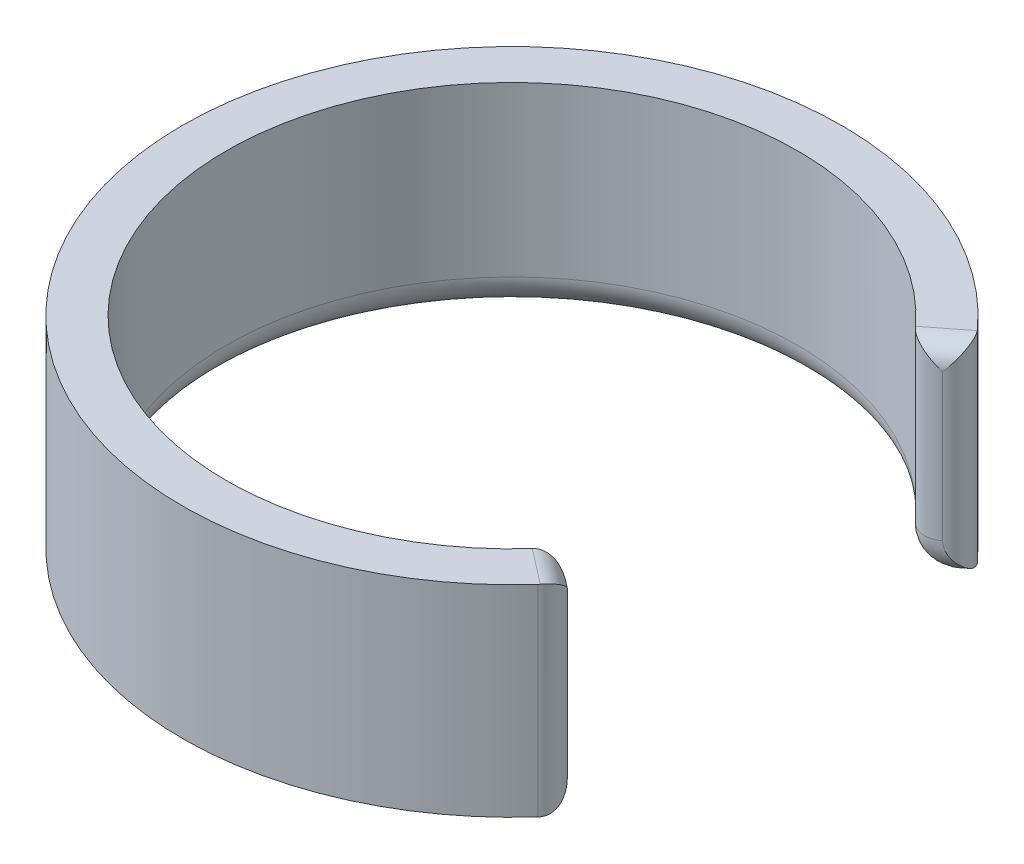
SolidWorks part; units mm, degrees
ref_plane "Front" through (0, 0, 0) normal (0, 0, 1) x (1, 0, 0)
ref_plane "Top" through (0, 0, 0) normal (0, 1, 0) x (1, 0, 0)
ref_plane "Right" through (0, 0, 0) normal (1, 0, 0) x (0, 0, -1)
sketch "Sketch1" plane through (0, 0, 0) normal (0, 1, 0) x (1, 0, 0)
  line L0 (5.1434, -3.9744) -> (5.9347, -4.5858)
  line L3 (5.1235, 4) -> (5.9117, 4.6154)
  arc A0 (5.1235, 4) -> (5.1434, -3.9744) centre (0, 0) ccw
  arc A2 (5.9117, 4.6154) -> (5.9347, -4.5858) centre (0, 0) ccw
  circle A3 centre (0, 0) radius 7.5 construction
  circle A4 centre (0, 0) radius 6.5 construction
  dimension "D1" = 1
  dimension "D2" = 5.1235
extrude "Boss-Extrude1" add sketch "Sketch1" along normal up to vertex (4.5833 mm away) contours A0
fillet "Fillet1" radius 0.75 1 edges at (-6.5, 0, 0.0162)
fillet "Fillet2" radius 0.5 8 edges at (5.9347, 2.2916, 4.5858) (5.539, 4.5833, 4.2801) (5.1434, 2.6666, 3.9744) (5.1235, 2.6666, -4) (5.5176, 4.5833, -4.3077) (5.9117, 2.2916, -4.6154) (5.3172, 0.2197, 4.1087) (5.2966, 0.2197, -4.1352)
